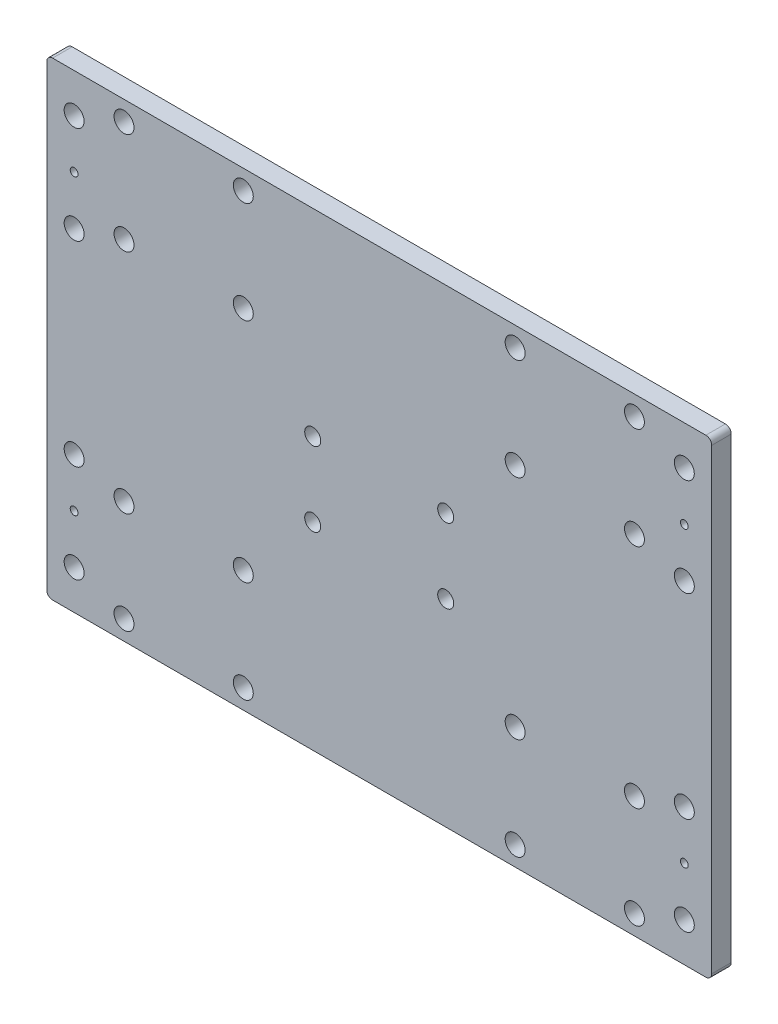
SolidWorks part; units mm, degrees
ref_plane "Front Plane" through (0, 0, 0) normal (0, 0, 1) x (1, 0, 0)
ref_plane "Top Plane" through (0, 0, 0) normal (0, 1, 0) x (1, 0, 0)
ref_plane "Right Plane" through (0, 0, 0) normal (1, 0, 0) x (0, 0, -1)
sketch "Sketch1" plane through (0, 0, 0) normal (0, 0, 1) x (1, 0, 0)
  line L1 (85, -60) -> (-85, -60)
  line L2 (85, -60) -> (85, 60)
  line L3 (85, 60) -> (-85, 60)
  line L4 (-85, -60) -> (-85, 60)
  line L5 (85, -60) -> (-85, 60) construction
  line L6 (85, 60) -> (-85, -60) construction
  point P0 (0, 0)
  dimension "D1" = 170
  dimension "D2" = 120
extrude "Boss-Extrude1" add sketch "Sketch1" along normal mid plane 5
sketch "Sketch2" plane through (0, 0, 2.5) normal (0, 0, 1) x (1, 0, 0)
  line L0 (-65.25, 71) -> (-65.25, -71) construction
  line L1 (65.25, -71) -> (65.25, 71) construction
  line L2 (-34.75, 71) -> (-34.75, -71) construction
  line L3 (34.75, -71) -> (34.75, 71) construction
  line L4 (70.6711, 55) -> (-71.3289, 55) construction
  line L5 (-71.3289, -55) -> (70.6711, -55) construction
  line L6 (70.6711, 29) -> (-71.3289, 29) construction
  line L7 (-71.3289, -29) -> (70.6711, -29) construction
  line L8 (85, 60) -> (-85, 60) construction
  line L9 (-85, -60) -> (85, -60) construction
  line L10 (-85, 60) -> (-85, -60) construction
  line L11 (85, -60) -> (85, 60) construction
  circle A0 centre (-65.25, 55) radius 2.55
  circle A1 centre (-34.75, 55) radius 2.55
  circle A2 centre (-34.75, 29) radius 2.55
  circle A3 centre (-65.25, 29) radius 2.55
  circle A4 centre (65.25, 55) radius 2.55
  circle A5 centre (65.25, 29) radius 2.55
  circle A6 centre (34.75, 29) radius 2.55
  circle A7 centre (34.75, 55) radius 2.55
  circle A8 centre (-65.25, -29) radius 2.55
  circle A9 centre (-34.75, -29) radius 2.55
  circle A10 centre (-34.75, -55) radius 2.55
  circle A11 centre (-65.25, -55) radius 2.55
  circle A12 centre (34.75, -29) radius 2.55
  circle A13 centre (65.25, -29) radius 2.55
  circle A14 centre (65.25, -55) radius 2.55
  circle A15 centre (34.75, -55) radius 2.55
  dimension "D1" = 5.1
  dimension "D2" = 5.1
  dimension "D3" = 5.1
  dimension "D4" = 5.1
  dimension "D5" = 5.1
  dimension "D6" = 5.1
  dimension "D7" = 5.1
  dimension "D8" = 5.1
  dimension "D9" = 5.1
  dimension "D10" = 5.1
  dimension "D11" = 5.1
  dimension "D12" = 5.1
  dimension "D13" = 5.1
  dimension "D14" = 5.1
  dimension "D15" = 5.1
  dimension "D16" = 5.1
  dimension "D17" = 5
  dimension "D18" = 5
  dimension "D19" = 26
  dimension "D20" = 26
  dimension "D21" = 30.5
  dimension "D22" = 30.5
  dimension "D23" = 19.75
  dimension "D24" = 19.75
extrude "Cut-Extrude1" cut sketch "Sketch2" against normal through all
sketch "Sketch4" plane through (0, 0, 2.5) normal (0, 0, 1) x (1, 0, 0)
  line L1 (-17, -9.5) -> (17, -9.5) construction
  line L2 (-17, -9.5) -> (-17, 9.5) construction
  line L3 (-17, 9.5) -> (17, 9.5) construction
  line L4 (17, -9.5) -> (17, 9.5) construction
  line L5 (-17, -9.5) -> (17, 9.5) construction
  line L6 (-17, 9.5) -> (17, -9.5) construction
  circle A0 centre (-17, 9.5) radius 2.05
  circle A1 centre (-17, -9.5) radius 2.05
  circle A2 centre (17, -9.5) radius 2.05
  circle A3 centre (17, 9.5) radius 2.05
  point P0 (0, 0)
  dimension "D3" = 4.1
  dimension "D4" = 4.1
  dimension "D5" = 4.1
  dimension "D6" = 4.1
  dimension "D1" = 34
  dimension "D2" = 19
extrude "Cut-Extrude3" cut sketch "Sketch4" against normal through all
fillet "Fillet1" radius 1.5 4 edges at (-85, -60, 0) (85, -60, 0) (85, 60, 0) (-85, 60, 0)
sketch "Sketch6" plane through (0, 0, 2.5) normal (0, 0, 1) x (1, 0, 0)
  line L0 (-78, -1002.1032) -> (-78, 48997.8968) construction
  line L1 (78, -1010.3548) -> (78, 48989.6452) construction
  line L2 (-85, 58.5) -> (-85, -58.5) construction
  line L3 (85, -58.5) -> (85, 58.5) construction
  line L4 (83.5, 60) -> (-83.5, 60) construction
  line L5 (-83.5, -60) -> (83.5, -60) construction
  circle A0 centre (-78, 50) radius 2.55
  circle A1 centre (-78, 37.5) radius 1
  circle A2 centre (-78, 25) radius 2.55
  circle A3 centre (-78, -25) radius 2.55
  circle A4 centre (-78, -37.5) radius 1
  circle A5 centre (-78, -50) radius 2.55
  dimension "D3" = 5.1
  dimension "D4" = 2
  dimension "D5" = 5.1
  dimension "D6" = 5.1
  dimension "D7" = 5.1
  dimension "D8" = 2
  dimension "D9" = 10
  dimension "D12" = 35
  dimension "D14" = 10
  dimension "D1" = 7
  dimension "D2" = 7
  dimension "D10" = 22.5
  dimension "D11" = 35
  dimension "D13" = 22.5
extrude "Cut-Extrude5" cut sketch "Sketch6" against normal through all
mirror "Mirror1" about plane through (0, 0, 0) normal (1, 0, 0) of "Cut-Extrude5"
equation "\"D23@Sketch2\"=5.75+14"
equation "\"D24@Sketch2\"=5.75+14"
equation "\"D6@Sketch4\"=\"D3@Sketch4\""
equation "\"D4@Sketch4\"=\"D3@Sketch4\""
equation "\"D5@Sketch4\"=\"D3@Sketch4\""
equation "\"D5@Sketch6\"=\"D3@Sketch6\""
equation "\"D6@Sketch6\" = \"D3@Sketch6\""
equation "\"D7@Sketch6\"=\"D3@Sketch6\""
